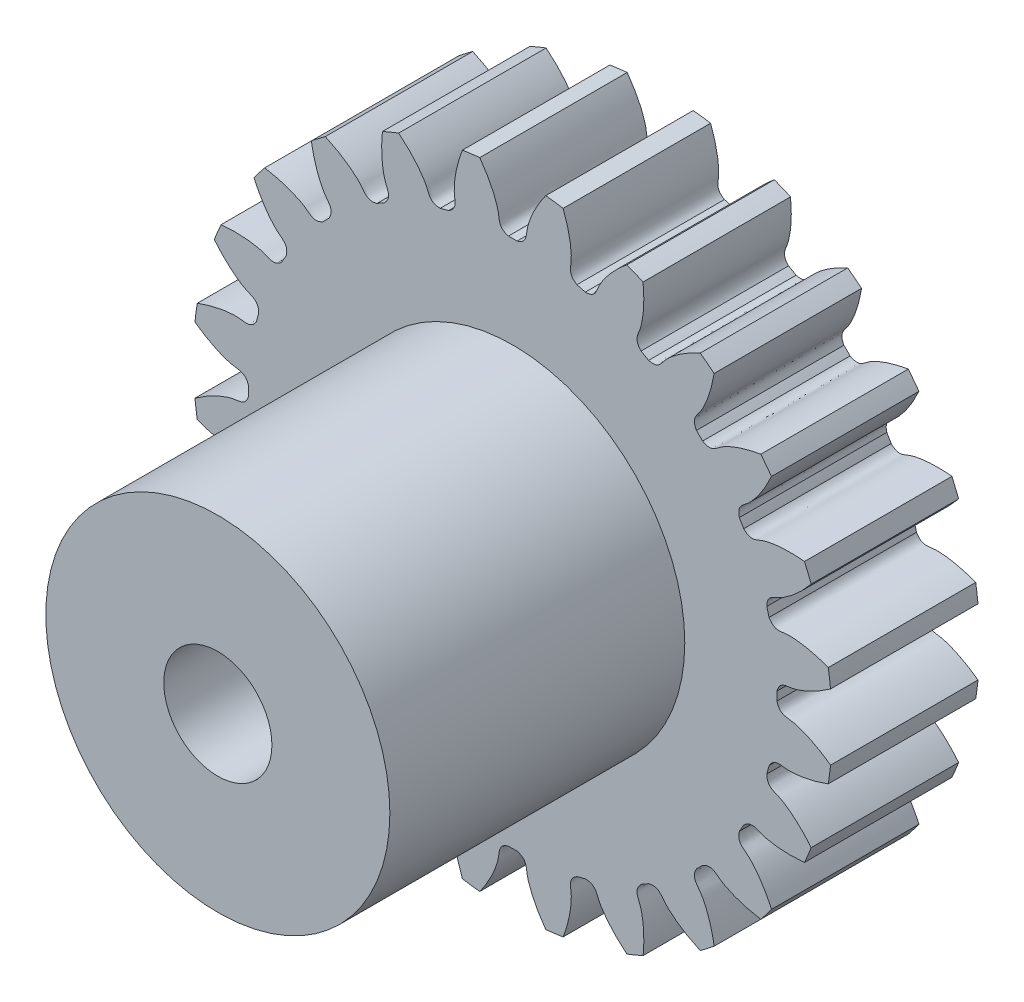
SolidWorks part; units mm, degrees
ref_plane "前视基准面" through (0, 0, 0) normal (0, 0, 1) x (1, 0, 0)
ref_plane "上视基准面" through (0, 0, 0) normal (0, 1, 0) x (1, 0, 0)
ref_plane "右视基准面" through (0, 0, 0) normal (1, 0, 0) x (0, 0, -1)
other "Configuration Table"
sketch "草图1" plane through (0, 0, 0) normal (0, 0, 1) x (1, 0, 0)
  circle A0 centre (0, 0) radius 6.5
extrude "凸台-拉伸1" add sketch "草图1" along normal blind 3
ref_axis "基准轴1" through (0, 0, 3) along (0, 0, -1)
sketch "草图2" plane through (0, 0, 0) normal (0, 0, 1) x (1, 0, 0)
  line L0 (0, 0) -> (0, 6.5) construction
  circle A0 centre (0, 0) radius 6.5 construction
  arc A1 (0.0884, 5.3743) -> (-0.0884, 5.3743) centre (0, 0) ccw
  arc A2 (1.5578, 7.3471) -> (-1.5578, 7.3471) centre (0, 0) ccw
  spline S0 degree 3 poles (0.0884, 5.3743) (0.284, 5.4284) (0.2695, 5.5579) (0.2931, 5.6863) (0.2965, 5.7029) (0.3007, 5.7216) (0.3058, 5.7424) (0.312, 5.7653) (0.3191, 5.7902) (0.3275, 5.8171) (0.3371, 5.846) (0.348, 5.8769) (0.3604, 5.9096) (0.3742, 5.9441) (0.3896, 5.9805) (0.4067, 6.0185) (0.4254, 6.0583) (0.446, 6.0997) (0.4684, 6.1427) (0.4928, 6.1872) (0.5192, 6.2332) (0.5476, 6.2806) (0.5782, 6.3293) (0.611, 6.3792) (0.6461, 6.4304) (0.6834, 6.4827) (0.7232, 6.536) (0.7654, 6.5903) (0.8101, 6.6456) (0.8574, 6.7016) (0.9073, 6.7583) (0.9598, 6.8158) (1.015, 6.8738) (1.0729, 6.9322) (1.1336, 6.9911) (1.1972, 7.0503) (1.2635, 7.1097) (1.3328, 7.1693) (1.4302, 7.2497) (1.506, 7.3084) (1.5578, 7.3471) knots 0 0 0 0 0.143961 0.149818 0.156577 0.164236 0.172796 0.182258 0.19262 0.203884 0.216049 0.229115 0.243082 0.25795 0.273719 0.290389 0.30796 0.326433 0.345806 0.366081 0.387257 0.409333 0.432311 0.45619 0.48097 0.506651 0.533234 0.560717 0.589101 0.618387 0.648574 0.679661 0.71165 0.74454 0.778331 0.813023 0.848616 0.885111 0.922506 1 1 1 1
  spline S1 degree 3 poles (-0.0884, 5.3743) (-0.284, 5.4284) (-0.2695, 5.5579) (-0.2931, 5.6863) (-0.2965, 5.7029) (-0.3007, 5.7216) (-0.3058, 5.7424) (-0.312, 5.7653) (-0.3191, 5.7902) (-0.3275, 5.8171) (-0.3371, 5.846) (-0.348, 5.8769) (-0.3604, 5.9096) (-0.3742, 5.9441) (-0.3896, 5.9805) (-0.4067, 6.0185) (-0.4254, 6.0583) (-0.446, 6.0997) (-0.4684, 6.1427) (-0.4928, 6.1872) (-0.5192, 6.2332) (-0.5476, 6.2806) (-0.5782, 6.3293) (-0.611, 6.3792) (-0.6461, 6.4304) (-0.6834, 6.4827) (-0.7232, 6.536) (-0.7654, 6.5903) (-0.8101, 6.6456) (-0.8574, 6.7016) (-0.9073, 6.7583) (-0.9598, 6.8158) (-1.015, 6.8738) (-1.0729, 6.9322) (-1.1336, 6.9911) (-1.1972, 7.0503) (-1.2635, 7.1097) (-1.3328, 7.1693) (-1.4302, 7.2497) (-1.506, 7.3084) (-1.5578, 7.3471) knots 0 0 0 0 0.143961 0.149818 0.156577 0.164236 0.172796 0.182258 0.19262 0.203884 0.216049 0.229115 0.243082 0.25795 0.273719 0.290389 0.30796 0.326433 0.345806 0.366081 0.387257 0.409333 0.432311 0.45619 0.48097 0.506651 0.533234 0.560717 0.589101 0.618387 0.648574 0.679661 0.71165 0.74454 0.778331 0.813023 0.848616 0.885111 0.922506 1 1 1 1
extrude "切除-拉伸1" cut sketch "草图2" along normal through all
pattern_circular "阵列(圆周)1" count 24 every 15 about axis through (0, 0, 3) along (0, 0, -1) of "切除-拉伸1"
sketch "草图3" plane through (0, 0, 0) normal (0, 0, 1) x (1, 0, 0)
  circle A0 centre (0, 0) radius 6 construction
  dimension "Dn" = 12
sketch "草图5" plane through (0, 0, 3) normal (0, 0, 1) x (1, 0, 0)
  circle A0 centre (0, 0) radius 3.5
  dimension "D1" = 7
extrude "凸台-拉伸2" add sketch "草图5" along normal blind 6
sketch "草图4" plane through (0, 0, 3) normal (0, 0, 1) x (1, 0, 0)
  circle A0 centre (0, 0) radius 1.1
  dimension "D1" = 2.2
extrude "切除-拉伸2" cut sketch "草图4" along normal up to next from surface starting at face at (0, 0, 0)
